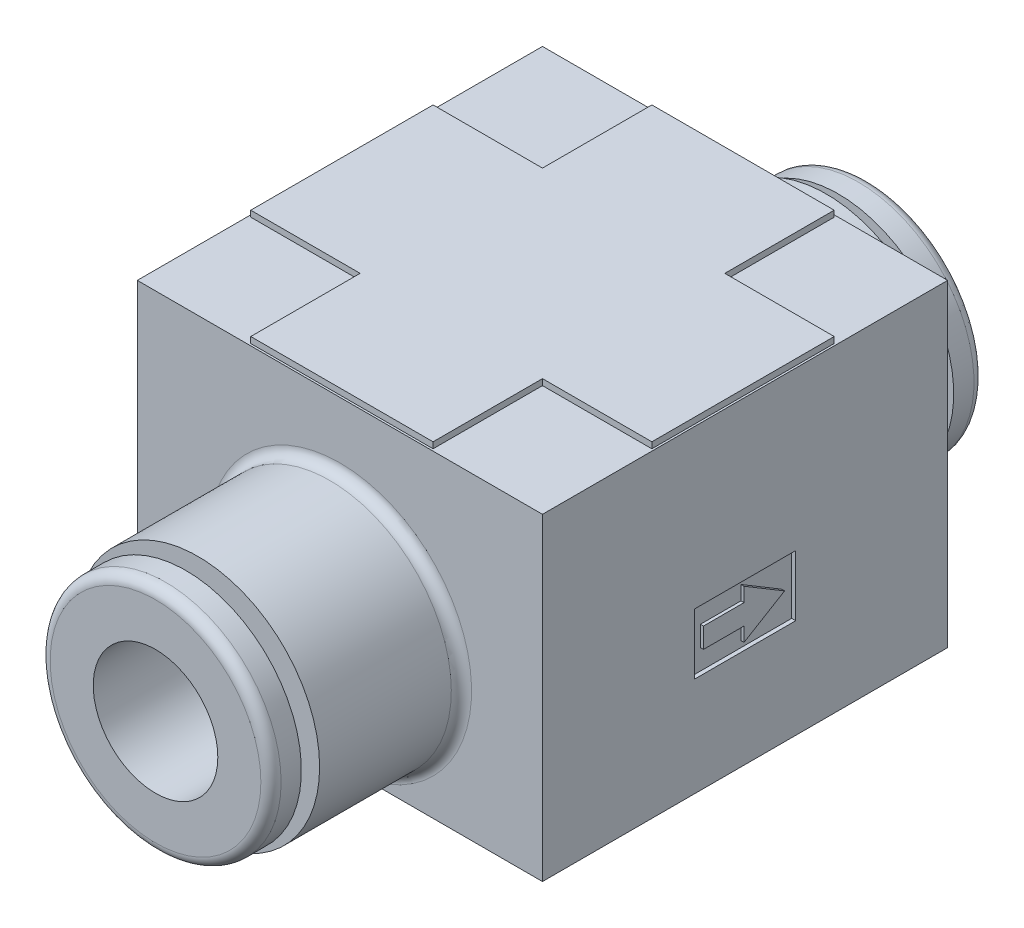
SolidWorks part; units mm, degrees
note: '?' marks a value the reader was unsure of.
ref_plane "Front" through (0, 0, 0) normal (0, 0, 1) x (1, 0, 0)
ref_plane "Top" through (0, 0, 0) normal (0, 1, 0) x (1, 0, 0)
ref_plane "Right" through (0, 0, 0) normal (1, 0, 0) x (0, 0, -1)
ref_axis "X-Axis" through (-80.9, 0, 0) along (1, 0, 0)?
ref_axis "Y-Axis" through (0, -50, 0) along (0, 1, 0)?
ref_axis "Z-Axis" through (0, 0, -80.9) along (0, 0, 1)
sketch "Sketch1" plane through (0, 0, 0) normal (0, 0, 1) x (1, 0, 0)
  line L1 (-10, -6.4) -> (10, -6.4)
  line L2 (-10, -6.4) -> (-10, 9.3)
  line L3 (-10, 9.3) -> (10, 9.3)
  line L4 (10, -6.4) -> (10, 9.3)
  line L5 (-10, -6.4) -> (10, 9.3) construction
  line L6 (-10, 9.3) -> (10, -6.4) construction
  point P0 (0, 1.45)
  dimension "D1" = 20
  dimension "D2" = 15.7
  dimension "D3" = 9.3
extrude "Boss-Extrude1" add sketch "Sketch1" along normal mid plane 20
ref_plane "Plane2" through (0, 0, 17) normal (0, 0, 1) x (1, 0, 0)
ref_plane "Plane3" through (0, 0, -14) normal (0, 0, 1) x (1, 0, 0)
sketch "Sketch3" plane through (0, 0, 0) normal (0, 0, 1) x (1, 0, 0)
  circle A0 centre (0, 0) radius 6
  dimension "D1" = 12
extrude "Boss-Extrude2" add sketch "Sketch3" along normal up to surface (17 mm away) and the other way up to surface (14 mm away) up to plane "Plane2" other way up to plane "Plane3"
fillet "Fillet1" radius 0.5 2 edges at (-6, 0, -10) (-6, 0, 10)
sketch "Sketch4" plane through (10, 0, 0) normal (1, 0, 0) x (0, 0, -1)
  line L1 (-2.5, -1.5) -> (2.5, -1.5)
  line L2 (-2.5, -1.5) -> (-2.5, 1.5)
  line L3 (-2.5, 1.5) -> (2.5, 1.5)
  line L4 (2.5, -1.5) -> (2.5, 1.5)
  line L5 (-2.5, -1.5) -> (2.5, 1.5) construction
  line L6 (-2.5, 1.5) -> (2.5, -1.5) construction
  point P0 (0, 0)
  dimension "D1" = 5
  dimension "D2" = 3
extrude "Cut-Extrude1" cut sketch "Sketch4" against normal blind 0.2
sketch "Sketch5" plane through (9.8, 0, 0) normal (1, 0, 0) x (0, 0, -1)
  line L0 (0, 1.2) -> (2, 0)
  line L1 (2, 0) -> (0, -1.2)
  line L2 (0, -1.2) -> (0, -0.5)
  line L3 (0, 0.5) -> (-2, 0.5)
  line L4 (-2, 0.5) -> (-2, -0.5)
  line L5 (-2, -0.5) -> (0, -0.5)
  line L6 (0, 1.2) -> (0, 0.5)
  line L7 (-2, 0) -> (2, 0) construction
  dimension "D1" = 4
  dimension "D2" = 1
  dimension "D3" = 2.4
  dimension "D4" = 2
extrude "Boss-Extrude3" add sketch "Sketch5" along normal blind 0.15
hole_wizard "M5 Ports" [suppressed] positions "3DSketch1" profile "Sketch6" hole size "M5x0.8" standard "ANSI Metric"
sketch3d "3DSketch1"
  point P0 (0, 0, 11)
  point P2 (0, 0, -11)
sketch "Sketch6" plane through (0, 0, 11) normal (1, 0, 0) x (0, -1, 0)
  line L0 (0, 0) -> (0, 5)
  line L1 (0, 5) -> (2.1, 5)
  line L2 (2.1, 5) -> (2.1, 0)
  line L5 (2.1, 0) -> (0, 0)
  line L10 (0, 5) -> (-2.1, 5) construction
  line L11 (0, -6.35) -> (0, 107.95) construction
  dimension "Hole Dia." = 4.2
  dimension "Hole Depth" = 5
  dimension "Drill Angle" = 180
chamfer "M5 Port Chamfer" [suppressed] distance 0.25 angle 45
hole_wizard "M6 Ports" [suppressed] positions "3DSketch2" profile "Sketch7" hole size "M6x1.0" standard "ANSI Metric"
sketch3d "3DSketch2"
  point P0 (0, 0, 11)
  point P2 (0, 0, -11)
sketch "Sketch7" plane through (0, 0, 11) normal (1, 0, 0) x (0, -1, 0)
  line L0 (0, 0) -> (0, 5)
  line L1 (0, 5) -> (2.5, 5)
  line L2 (2.5, 5) -> (2.5, 0)
  line L5 (2.5, 0) -> (0, 0)
  line L10 (0, 5) -> (-2.5, 5) construction
  line L11 (0, -6.35) -> (0, 107.95) construction
  dimension "Hole Dia." = 5
  dimension "Hole Depth" = 5
  dimension "Drill Angle" = 180
chamfer "Chamfer2" [suppressed] distance 0.3 angle 45
sketch "Sketch8" plane through (0, 0, 0) normal (1, 0, 0) x (0, 0, -1)
  line L0 (-17, 0) -> (-19.1, 0)
  line L2 (-17, 6) -> (-17, -6) construction
  line L3 (-19.1, 0) -> (-19.1, 5.7)
  line L4 (-19.1, 5.7) -> (-17.6, 5.7)
  line L5 (-17.6, 5.7) -> (-17.6, 3.15)
  line L6 (-17.6, 3.15) -> (-17, 3.15)
  line L7 (-17, 3.15) -> (-17, 0)
  dimension "D1" = 3.15
  dimension "D2" = 0.6
  dimension "D3" = 5.7
  dimension "D4" = 2.1
revolve "Revolve2" add sketch "Sketch8" angle 360 about axis through (0, 0, -80.9) along (0, 0, 1)
ref_plane "Plane1" through (0, 0, 1.5) normal (0, 0, 1) x (1, 0, 0)
mirror "Mirror1" about plane through (0, 0, 1.5) normal (0, 0, 1) of "Revolve2"
fillet "Fillet2" radius 0.5 4 edges at (-5.7, 0, 19.1) (-3.15, 0, 17.6) (-5.7, 0, -16.1) (-3.15, 0, -14.6)
hole_wizard "One Touch Port" positions "3DSketch3" profile "Sketch9" hole size "M4x0.7" standard "ANSI Metric"
sketch3d "3DSketch3"
  point P0 (0, 0, 19.1)
  point P2 (0, 0, -16.1)
sketch "Sketch9" plane through (0, 0, 19.1) normal (1, 0, 0) x (0, -1, 0)
  line L0 (0, 0) -> (0, 6)
  line L1 (0, 6) -> (3.075, 6)
  line L2 (3.075, 6) -> (3.075, 0)
  line L5 (3.075, 0) -> (0, 0)
  line L10 (0, 6) -> (-3.075, 6) construction
  line L11 (0, -6.35) -> (0, 107.95) construction
  dimension "Hole Dia." = 6.15
  dimension "Hole Depth" = 6
  dimension "Drill Angle" = 180
fillet "Fillet3" [suppressed] radius 0.3
hole_wizard "1/8 One Touch Port" [suppressed] positions "3DSketch4" profile "Sketch10" hole size "1/8" standard "ANSI Inch"
sketch3d "3DSketch4" [suppressed]
  circle A0 centre (0, 0, -15.6) radius 4.55 construction
  point P0 (0, 0, 19.8)
  point P2 (0, 0, -15.6)
  point P6 (0, 0, -11.05)
  point P7 (0, 0, -16.1)
sketch "Sketch10" plane through (0, 0, 19.8) normal (1, 0, 0) x (0, -1, 0)
  line L0 (0, 0) -> (0, 5)
  line L1 (0, 5) -> (1.5875, 5)
  line L2 (1.5875, 5) -> (1.5875, 0)
  line L5 (1.5875, 0) -> (0, 0)
  line L10 (0, 5) -> (-1.5875, 5) construction
  line L11 (0, -6.35) -> (0, 107.95) construction
  dimension "Hole Dia." = 3.175
  dimension "Hole Depth" = 5
  dimension "Drill Angle" = 180
fillet "Fillet4" [suppressed] radius 0.25
sketch "Sketch11" plane through (0, 9.3, 0) normal (0, 1, 0) x (1, 0, 0)
  line L0 (10, -10) -> (10, 10) construction
  line L1 (-9.9, -4.5) -> (-4.5, -4.5)
  line L2 (-9.9, -4.5) -> (-9.9, 4.5)
  line L3 (-9.9, 4.5) -> (-4.5, 4.5)
  line L4 (9.9, -4.5) -> (9.9, 4.5)
  line L5 (-9.9, -4.5) -> (9.9, 4.5) construction
  line L6 (-9.9, 4.5) -> (9.9, -4.5) construction
  line L7 (10, 10) -> (-10, 10) construction
  line L8 (-4.5, -9.9) -> (4.5, -9.9)
  line L9 (-4.5, -9.9) -> (-4.5, -4.5)
  line L10 (-4.5, 9.9) -> (4.5, 9.9)
  line L11 (4.5, -9.9) -> (4.5, -4.5)
  line L12 (-4.5, -9.9) -> (4.5, 9.9) construction
  line L13 (-4.5, 9.9) -> (4.5, -9.9) construction
  line L14 (4.5, 4.5) -> (9.9, 4.5)
  line L15 (4.5, 4.5) -> (4.5, 9.9)
  line L16 (4.5, -4.5) -> (9.9, -4.5)
  line L17 (-4.5, 4.5) -> (-4.5, 9.9)
  point P0 (0, 0)
  point P8 (0, 0)
  dimension "D1" = 0.1
  dimension "D2" = 9
  dimension "D3" = 0.1
  dimension "D4" = 9
extrude "Boss-Extrude4" add sketch "Sketch11" along normal blind 0.3
